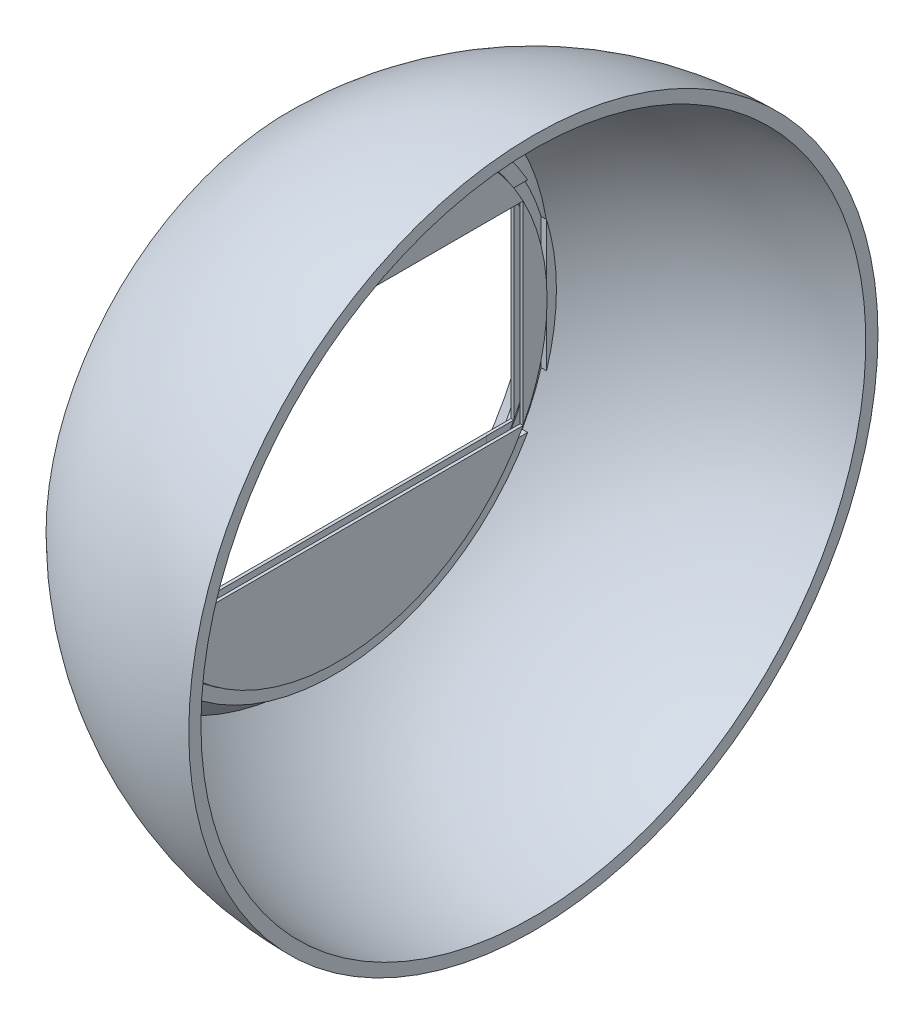
SolidWorks part; units mm, degrees
ref_plane "Front Plane" through (0, 0, 0) normal (0, 0, 1) x (1, 0, 0)
ref_plane "Top Plane" through (0, 0, 0) normal (0, 1, 0) x (1, 0, 0)
ref_plane "Right Plane" through (0, 0, 0) normal (1, 0, 0) x (0, 0, -1)
sketch "Sketch1" plane through (0, 0, 0) normal (0, 0, 1) x (1, 0, 0)
  line L0 (-112.6487, 0) -> (112.6487, 0) construction
  line L1 (-40.2069, 40) -> (-34.8287, 34.6218)
  line L2 (-34.8287, 34.6218) -> (-32.8287, 34.6218)
  line L3 (-37.3564, 39.9779) -> (-34.0002, 36.6218)
  line L4 (-34.0002, 36.6218) -> (-32.8287, 36.6218)
  line L5 (0, 56.715) -> (0, 54.715)
  line L6 (-32.8287, 36.6218) -> (-32.8287, 34.6218)
  arc A0 (0, 56.715) -> (-40.2069, 40) centre (0, 0) ccw
  arc A1 (0, 54.715) -> (-37.3564, 39.9779) centre (0, 0) ccw
  point P4 (0, 0)
  dimension "D1" = 40
  dimension "D2" = 2
  dimension "D3" = 2
revolve "Revolve1" add sketch "Sketch1" angle 360 about L0
ref_plane "Plane1" through (-34.185, 0, 0) normal (1, 0, 0) x (0, 0, -1)
sketch "Sketch7" plane through (-34.185, 0, 0) normal (1, 0, 0) x (0, 0, -1)
  line L1 (-30.5, 16) -> (30.5, 16)
  line L2 (-30.5, 16) -> (-30.5, -16)
  line L3 (-30.5, -16) -> (30.5, -16)
  line L4 (30.5, 16) -> (30.5, -16)
  circle A0 centre (0, 0) radius 34.442
  dimension "D1" = 32
  dimension "D2" = 61
extrude "Boss-Extrude1" add sketch "Sketch7" along normal blind 2 separate body contours L1 A0 | L2 A0 | L3 A0 | L4 A0 region at (-34.185, 23.5776, 0) region at (-34.185, 0, 32.0848) region at (-34.185, 0, -32.0848) region at (-34.185, -23.5776, 0)
sketch "Sketch9" plane through (0, 16, 0) normal (0, -1, 0) x (1, 0, 0)
  line L0 (-32.185, 30.5) -> (-32.185, -30.5) construction
  line L1 (-33.685, 30.5) -> (-32.685, 30.5)
  line L2 (-33.685, 30.5) -> (-33.685, -30.5)
  line L3 (-33.685, -30.5) -> (-32.685, -30.5)
  line L4 (-32.685, 30.5) -> (-32.685, -30.5)
  line L5 (-33.685, 30.5) -> (-32.685, -30.5) construction
  line L6 (-33.685, -30.5) -> (-32.685, 30.5) construction
  point P0 (-33.185, 0)
  point P5 (0, 0)
  point P7 (0, 0)
  dimension "D1" = 61
  dimension "D2" = 1
  dimension "D3" = 1
extrude "Cut-Extrude1" cut sketch "Sketch9" against normal blind 2
sketch "Sketch10" plane through (0, -16, 0) normal (0, 1, 0) x (1, 0, 0)
  line L0 (-32.185, -30.5) -> (-32.185, 30.5) construction
  line L1 (-32.685, 30.5) -> (-33.685, 30.5)
  line L2 (-32.685, 30.5) -> (-32.685, -30.5)
  line L3 (-32.685, -30.5) -> (-33.685, -30.5)
  line L4 (-33.685, 30.5) -> (-33.685, -30.5)
  line L5 (-32.685, 30.5) -> (-33.685, -30.5) construction
  line L6 (-32.685, -30.5) -> (-33.685, 30.5) construction
  point P0 (-33.185, 0)
  point P5 (0, 0)
  point P7 (0, 0)
  dimension "D1" = 1
  dimension "D2" = 61
  dimension "D3" = 1
extrude "Cut-Extrude2" cut sketch "Sketch10" against normal blind 2
sketch "Sketch12" plane through (0, 0, 30.5) normal (0, 0, -1) x (-1, 0, 0)
  line L0 (34.185, 16) -> (34.185, -16) construction
  line L3 (32.685, 18) -> (33.685, 18)
  line L4 (32.685, 18) -> (32.685, -18)
  line L5 (32.685, -18) -> (33.685, -18)
  line L6 (33.685, 18) -> (33.685, -18)
  line L7 (32.685, 18) -> (33.685, -18) construction
  line L8 (32.685, -18) -> (33.685, 18) construction
  point P0 (0, 0)
  point P2 (33.185, 0)
  dimension "D1" = 1
  dimension "D2" = 1
  dimension "D3" = 36
extrude "Cut-Extrude3" cut sketch "Sketch12" against normal blind 2
sketch "Sketch13" plane through (0, 0, -30.5) normal (0, 0, 1) x (1, 0, 0)
  line L0 (-32.185, 16) -> (-32.185, -16) construction
  line L1 (-33.7254, 18) -> (-32.7254, 18)
  line L2 (-33.7254, 18) -> (-33.7254, -18)
  line L3 (-33.7254, -18) -> (-32.7254, -18)
  line L4 (-32.7254, 18) -> (-32.7254, -18)
  line L5 (-33.7254, 18) -> (-32.7254, -18) construction
  line L6 (-33.7254, -18) -> (-32.7254, 18) construction
  point P0 (-33.2254, 0)
  point P5 (0, 0)
  dimension "D1" = 1
  dimension "D2" = 1.0404
  dimension "D3" = 36
extrude "Cut-Extrude8" cut sketch "Sketch13" against normal mid plane 9
